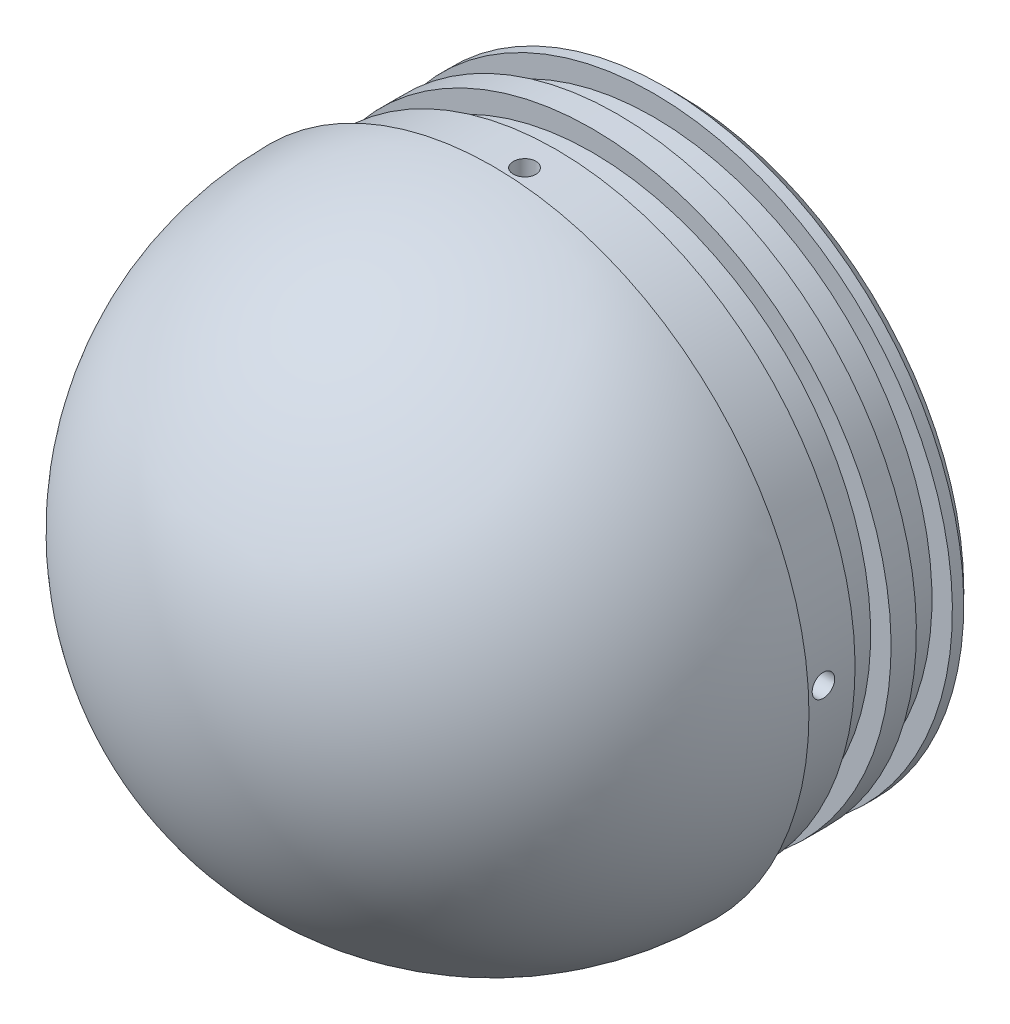
SolidWorks part; units mm, degrees
material "6061-T6 (SS)"
ref_plane "XY" through (0, 0, 0) normal (0, 0, 1) x (1, 0, 0)
ref_plane "XZ" through (0, 0, 0) normal (0, 1, 0) x (1, 0, 0)
ref_plane "YZ" through (0, 0, 0) normal (1, 0, 0) x (0, 0, -1)
ref_axis "X" through (-34.925, 0, 0) along (1, 0, 0)
ref_axis "Y" through (0, -34.925, 0) along (0, 1, 0)
ref_axis "Z" through (0, 0, 52.8066) along (0, 0, -1)
sketch "Sketch2" plane through (0, 0, 0) normal (1, 0, 0) x (0, 0, -1)
  line L2 (-18.542, 30.0292) -> (-12.192, 30.0292)
  line L3 (-12.192, 30.0292) -> (-12.192, 27.9781)
  line L4 (-12.192, 27.9781) -> (-8.5725, 27.9781)
  line L5 (-8.5725, 27.9781) -> (-8.5725, 30.0292)
  line L6 (-8.5725, 30.0292) -> (-6.0325, 30.0292)
  line L7 (-6.0325, 30.0292) -> (-6.0325, 27.9781)
  line L8 (-6.0325, 27.9781) -> (-2.413, 27.9781)
  line L9 (-2.413, 27.9781) -> (-2.413, 30.0292)
  line L10 (-2.413, 30.0292) -> (0, 30.0292)
  line L11 (0, 30.0292) -> (0, 0)
  line L12 (0, 0) -> (-18.542, 0)
  line L13 (-18.542, 30.0292) -> (-18.542, 0)
  dimension "D1" = 30.0292
  dimension "D2" = 27.9781
  dimension "D3" = 3.6195
  dimension "D4" = 2.54
  dimension "D5" = 2.413
  dimension "D7" = 6.35
revolve "Revolve1" add sketch "Sketch2" angle 360 about L12
hole_wizard "#4-40 Tapped Hole1" positions "3DSketch1" profile "Sketch3" tap size "#4-40" standard "ANSI Inch"
sketch3d "3DSketch1"
  line L0 (0, 0, 0) -> (0, 0, 15.367)
  line L1 (0, 0, 15.367) -> (-30.0292, 0, 15.367)
  line L3 (30.0292, 0, 15.367) -> (0, -30.0292, 15.367)
  line L5 (0, -30.0292, 15.367) -> (-30.0292, 0, 15.367)
  line L9 (0, 0, 15.367) -> (0, -30.0292, 15.367)
  line L11 (0, 0, 15.367) -> (30.0292, 0, 15.367)
  line L13 (0, 0, 15.367) -> (0, 30.0292, 15.367)
  line L15 (0, -30.0292, 12.192) -> (0, -30.0292, 18.542)
  line L16 (0, 30.0292, 15.367) -> (-30.0292, 0, 15.367)
  line L18 (30.0292, 0, 15.367) -> (0, 30.0292, 15.367)
  circle A1 centre (0, 0, 12.192) radius 30.0292 construction
  circle A2 centre (0, 0, 18.542) radius 30.0292 construction
  point P5 (0, -30.0292, 15.367)
  point P7 (30.0292, 0, 15.367)
  point P20 (-30.0292, 0, 15.367)
  point P1370 (0, 0, -17.8372)
  point P1373 (0, 0, -11.4872)
  point P1390 (0, 30.0292, 15.367)
cosmetic thread "Hole Thread2"
cosmetic thread "Hole Thread3"
cosmetic thread "Hole Thread5"
cosmetic thread "Hole Thread6"
sketch "Sketch3" plane through (0, -30.0292, 15.367) normal (1, 0, 0) x (0, 0, -1)
  line L0 (0, 0) -> (0, 8.2992)
  line L1 (0, 8.2992) -> (1.1303, 7.62)
  line L2 (1.1303, 7.62) -> (1.1303, 0)
  line L5 (1.1303, 0) -> (0, 0)
  line L10 (0, 8.2992) -> (-1.1303, 7.62) construction
  line L11 (0, -6.35) -> (0, 107.95) construction
  dimension "Tap Drill Dia." = 2.2606
  dimension "Tap Drill Depth" = 7.62
  dimension "Drill Angle" = 118
sketch "Sketch6" plane through (0, 0, 0) normal (0, 1, 0) x (1, 0, 0)
  line L0 (0, -18.542) -> (31.75, -18.542)
  line L2 (0, -18.542) -> (0, -50.292)
  line L4 (12.7, -18.542) -> (0, -18.542) construction
  line L6 (-30.0292, -18.542) -> (30.0292, -18.542) construction
  arc A0 (0, -50.292) -> (31.75, -18.542) centre (0, -18.542) ccw
  dimension "D1" = 31.75
  dimension "D2" = 19.05
revolve "Revolve2" add sketch "Sketch6" angle 360 about L2 other way angle 360
ref_plane "Plane1" through (0, 0, 50.292) normal (0, 0, 1) x (1, 0, 0)
sketch "Sketch10" plane through (0, 0, 0) normal (0, 0, -1) x (-1, 0, 0)
  circle A0 centre (0, 0) radius 20.5041
  dimension "D1" = 41.0083
extrude "Cut-Extrude3" cut sketch "Sketch10" against normal blind 31.75
hole_wizard "#4-40 Tapped Hole2" positions "Sketch11" profile "Sketch12" tap size "#4-40" standard "ANSI Inch"
sketch "Sketch11" plane through (0, 0, 31.75) normal (0, 0, -1) x (-1, 0, 0)
  line L2 (20.5041, 0) -> (-20.5041, 0) construction
  circle A1 centre (0, 0) radius 20.5041 construction
  point P25 (0, 0)
cosmetic thread "Hole Thread8" parameters "D1"=5.588, "D2"=2.8448
sketch "Sketch12" plane through (0, 0, 31.75) normal (1, 0, 0) x (0, 1, 0)
  line L0 (0, 0) -> (0, 8.2992)
  line L1 (0, 8.2992) -> (1.1303, 7.62)
  line L2 (1.1303, 7.62) -> (1.1303, 0)
  line L5 (1.1303, 0) -> (0, 0)
  line L10 (0, 8.2992) -> (-1.1303, 7.62) construction
  line L11 (0, -6.35) -> (0, 107.95) construction
  dimension "Tap Drill Dia." = 2.2606
  dimension "Tap Drill Depth" = 7.62
  dimension "Drill Angle" = 118
sketch "Sketch14" [suppressed] plane through (0, 0, 0) normal (0, 0, -1) x (-1, 0, 0)
  line L0 (-26.6658, -3.175) -> (-20.2568, -3.175)
  line L1 (-20.2568, -3.175) -> (-20.2568, 3.175)
  line L2 (-20.2568, 3.175) -> (-26.6658, 3.175)
  line L3 (0, 0) -> (-20.2568, 0) construction
  line L4 (-3.175, 26.6658) -> (-3.175, 20.2568)
  line L5 (-3.175, 20.2568) -> (3.175, 20.2568)
  line L6 (3.175, 20.2568) -> (3.175, 26.6658)
  line L7 (26.6658, 3.175) -> (20.2568, 3.175)
  line L8 (20.2568, 3.175) -> (20.2568, -3.175)
  line L9 (20.2568, -3.175) -> (26.6658, -3.175)
  line L10 (3.175, -26.6658) -> (3.175, -20.2568)
  line L11 (3.175, -20.2568) -> (-3.175, -20.2568)
  line L12 (-3.175, -20.2568) -> (-3.175, -26.6658)
  line L13 (0, 0) -> (0, 20.2568) construction
  arc A0 (-26.6658, -3.175) -> (-3.175, -26.6658) centre (0, 0) ccw
  circle A1 centre (0, 0) radius 30.0292 construction
  arc A2 (3.175, -26.6658) -> (26.6658, -3.175) centre (0, 0) ccw
  arc A3 (-3.175, 26.6658) -> (-26.6658, 3.175) centre (0, 0) ccw
  arc A4 (26.6658, 3.175) -> (3.175, 26.6658) centre (0, 0) ccw
  circle A5 centre (0, 0) radius 20.5041 construction
  dimension "D1" = 3.175
  dimension "D2" = 6.35
  dimension "D4" = 4
extrude "Cut-Extrude4" [suppressed] cut sketch "Sketch14" against normal offset from surface (30.48 mm away) 5.08 contours L10 L11 L12 A0 L0 L1 L2 A3 L4 L5 L6 A4 L7 L8 L9 A2 up to face at (-1.1303, 0, 31.75)
fillet "Fillet1" [suppressed] radius 6.858
sketch "Sketch13" plane through (0, 0, 31.75) normal (0, 0, -1) x (-1, 0, 0)
  circle A0 centre (0, 0) radius 20.5041
  circle A1 centre (0, 0) radius 20.5041 construction
extrude "Boss-Extrude1" [suppressed] add sketch "Sketch13" along normal up to surface (31.75 mm away) separate body up to face at (0, 20.5041, 0)
chamfer "Chamfer1" distance 1.27 angle 45 1 edges at (0, 30.0292, 0)
